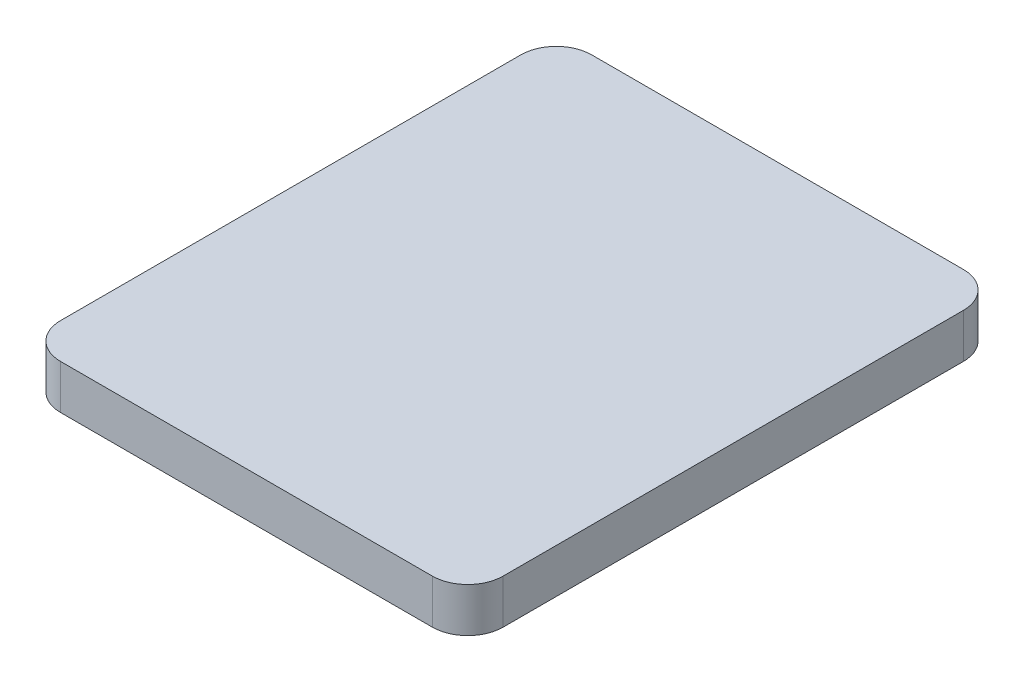
SolidWorks part; units mm, degrees
material "Acrylic (Medium-high impact)"
ref_plane "Front Plane" through (0, 0, 0) normal (0, 0, 1) x (1, 0, 0)
ref_plane "Top Plane" through (0, 0, 0) normal (0, 1, 0) x (1, 0, 0)
ref_plane "Right Plane" through (0, 0, 0) normal (1, 0, 0) x (0, 0, -1)
ref_plane "Plane1" through (0, 0, 0) normal (0, 1, 0) x (1, 0, 0)
sketch "Sketch1" plane through (0, 0, 0) normal (0, 1, 0) x (1, 0, 0)
  line L1 (0, 0) -> (31.75, 0)
  line L2 (0, 0) -> (0, 38.1)
  line L3 (0, 38.1) -> (31.75, 38.1)
  line L4 (31.75, 0) -> (31.75, 38.1)
  dimension "D1" = 38.1
  dimension "D2" = 31.75
extrude "Boss-Extrude1" add sketch "Sketch1" along normal blind 3.175
ref_plane "Plane2" through (0, 3.175, 0) normal (0, 1, 0) x (1, 0, 0)
fillet "Fillet1" radius 2.54 4 edges at (0, 1.5875, -38.1) (31.75, 1.5875, -38.1) (31.75, 1.5875, 0) (0, 1.5875, 0)
